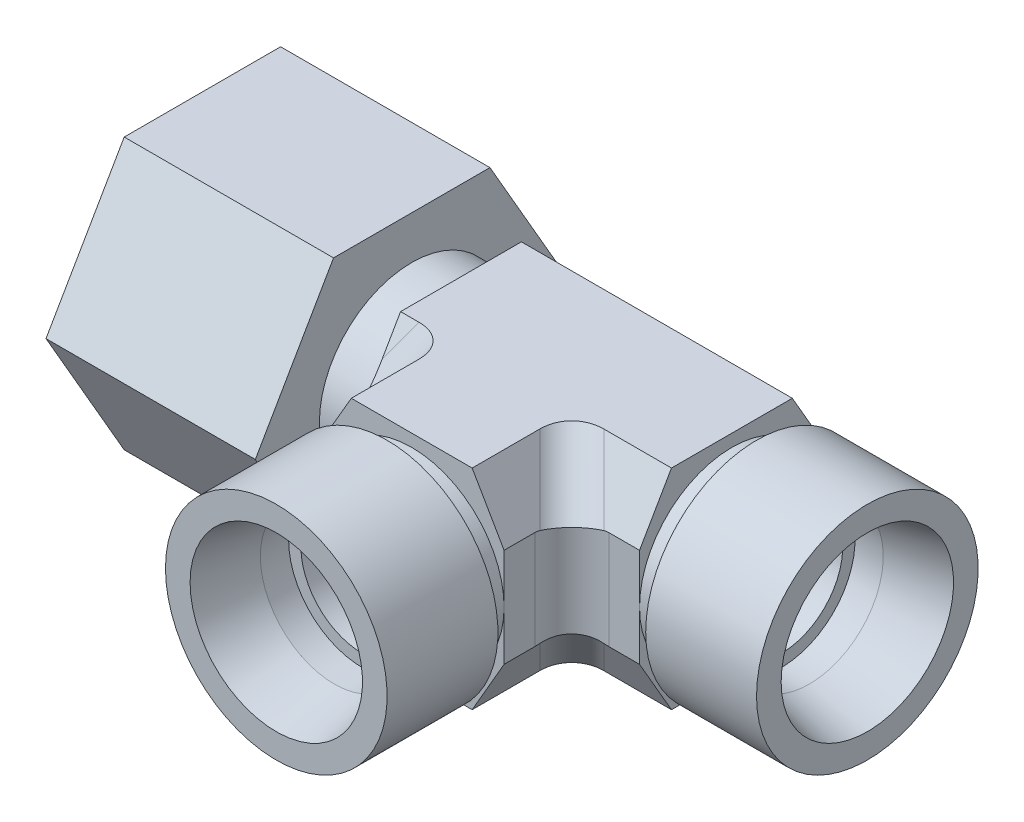
SolidWorks part; units mm, degrees
ref_plane "Plane1" through (0, 0, 0) normal (0, 0, 1) x (1, 0, 0)
ref_plane "Plane2" through (0, 0, 0) normal (0, 1, 0) x (1, 0, 0)
ref_plane "Plane3" through (0, 0, 0) normal (1, 0, 0) x (0, 0, -1)
sketch "Sketch1" plane through (0, 0, 0) normal (0, 1, 0) x (1, 0, 0)
  line L0 (-29.5, 0) -> (24, 0) construction
  line L1 (24, 0) -> (24, 9)
  line L2 (24, 9) -> (15, 9)
  line L3 (15, 9) -> (15, 7.5)
  line L4 (15, 7.5) -> (-13, 7.5)
  line L5 (-13, 7.5) -> (-13, 11)
  line L6 (-13, 11) -> (-30, 11)
  line L7 (-29.5, 6) -> (-29.5, 0)
  line L8 (-30, 11) -> (-30, 8.25)
  line L9 (-30, 8.25) -> (-23, 8.25)
  line L10 (-29.5, 0) -> (24, 0)
  line L12 (-23, 8.25) -> (-23, 6)
  line L13 (0, 0) -> (0, -32.9025) construction
  line L14 (-23, 6) -> (-29.5, 6)
  point P0 (-30, 0)
  dimension "Længde" = 54
  dimension "Indv. dia. omløber" = 16.5
  dimension "S3 længde" = 17
  dimension "Dybde på omløber" = 7
  dimension "L1" = 29.5
  dimension "M længde" = 9
revolve "Revolve1" add sketch "Sketch1" angle 360 about L10
sketch "Sketch2" plane through (0, 0, 0) normal (0, 1, 0) x (1, 0, 0)
  line L0 (0, 0) -> (0, -41.5691) construction
  line L1 (0, 0) -> (7.5, 0)
  line L2 (7.5, 0) -> (7.5, -15)
  line L3 (7.5, -15) -> (9, -15)
  line L4 (9, -15) -> (9, -24)
  line L5 (9, -24) -> (0, -24)
  line L6 (0, 0) -> (55.2214, 0) construction
  line L7 (0, 0) -> (0, -24)
  dimension "M længde" = 9
revolve "Revolve2" add sketch "Sketch2" angle 360 about L7
sketch "Sketch3" plane through (0, 0, 0) normal (1, 0, 0) x (0, 0, -1)
  line L0 (-7.5, 4.0096) -> (-7.5, -4.0096)
  line L1 (7.5, 4.0096) -> (4.9075, 8.5)
  line L2 (4.9075, 8.5) -> (-4.9075, 8.5)
  line L3 (-4.9075, 8.5) -> (-7.5, 4.0096)
  line L4 (-7.5, -4.0096) -> (-4.9075, -8.5)
  line L5 (-4.9075, -8.5) -> (4.9075, -8.5)
  line L6 (4.9075, -8.5) -> (7.5, -4.0096)
  line L7 (7.5, 4.0096) -> (7.5, -4.0096)
  circle A0 centre (0, 0) radius 8.5 construction
  circle A3 centre (0, 0) radius 7.5 construction
extrude "Extrude1" add sketch "Sketch3" along normal blind 9 and the other way blind 13
sketch "Sketch4" plane through (0, 0, 0) normal (0, 0, 1) x (1, 0, 0)
  line L0 (7.5, 4.0096) -> (7.5, -4.0096)
  line L1 (7.5, 4.0096) -> (4.9075, 8.5)
  line L2 (4.9075, 8.5) -> (-4.9075, 8.5)
  line L3 (-4.9075, 8.5) -> (-7.5, 4.0096)
  line L4 (-7.5, -4.0096) -> (-4.9075, -8.5)
  line L5 (-4.9075, -8.5) -> (4.9075, -8.5)
  line L6 (4.9075, -8.5) -> (7.5, -4.0096)
  line L7 (-7.5, 4.0096) -> (-7.5, -4.0096)
  circle A0 centre (0, 0) radius 8.5 construction
  circle A1 centre (0, 0) radius 7.5 construction
extrude "Extrude2" add sketch "Sketch4" along normal blind 13
sketch "Sketch5" plane through (0, 0, 0) normal (0, 1, 0) x (1, 0, 0)
  line L0 (-30, 0) -> (24, 0) construction
  line L1 (-30, 11) -> (-30, -11) construction
  line L2 (24, -9) -> (24, 9) construction
  line L3 (24, 0) -> (24, 7)
  line L4 (24, 7) -> (19.2954, 6)
  line L5 (19.2954, 6) -> (17, 6)
  line L6 (17, 6) -> (17, 5)
  line L7 (17, 5) -> (-5, 5)
  line L8 (-5, 5) -> (-5, 4)
  line L9 (-5, 4) -> (-30, 4)
  line L10 (-30, 4) -> (-30, 0)
  line L11 (0, 0) -> (0, -24) construction
  line L12 (-9, -24) -> (9, -24) construction
  line L13 (-30, 0) -> (24, 0)
  dimension "l" = 17
  dimension "samme som l8" = 7
  dimension "Indv. dia. (side m. omløber)" = 8
  dimension "vinkel" = 12
revolve "Cut-Revolve1" cut sketch "Sketch5" angle 360 about L13
sketch "Sketch6" plane through (0, 0, 0) normal (0, 1, 0) x (1, 0, 0)
  line L0 (0, 0) -> (0, -24) construction
  line L1 (-9, -24) -> (9, -24) construction
  line L2 (0, 0) -> (5, 0)
  line L3 (5, 0) -> (5, -17)
  line L4 (5, -17) -> (6, -17)
  line L5 (6, -17) -> (6, -19.2954)
  line L6 (6, -19.2954) -> (7, -24)
  line L7 (7, -24) -> (0, -24)
  line L8 (0, 0) -> (0, -24)
  dimension "l8" = 7
  dimension "vinkel" = 12
revolve "Cut-Revolve2" cut sketch "Sketch6" angle 360 about L0
sketch "Sketch7" plane through (-30, 0, 0) normal (-1, 0, 0) x (0, 0, 1)
  line L1 (-12.7017, 0) -> (-6.3509, -11)
  line L2 (-6.3509, -11) -> (6.3509, -11)
  line L3 (6.3509, -11) -> (12.7017, 0)
  line L4 (12.7017, 0) -> (6.3509, 11)
  line L5 (6.3509, 11) -> (-6.3509, 11)
  line L6 (-6.3509, 11) -> (-12.7017, 0)
  circle A0 centre (0, 0) radius 11 construction
  circle A1 centre (0, 0) radius 8.25 construction
  circle A2 centre (0, 0) radius 8.25
extrude "Extrude3" add sketch "Sketch7" against normal up to surface (17 mm away) up to face at (-13, 0, 11)
fillet "Fillet1" radius 3 6 edges at (6.2037, -6.2548, 6.2037) (6.2037, 6.2548, 6.2037) (-6.2037, -6.2548, 6.2037) (-6.2037, 6.2548, 6.2037) (7.5, 0, 7.5) (-7.5, 0, 7.5)
sketch "Sketch9" [suppressed] plane through (-43.8, 0, 0) normal (1, 0, 0) x (0, 0, -1)
  circle A0 centre (0, 0) radius 7 construction
  circle A1 centre (0, 0) radius 7
extrude "Cut-Extrude1" [suppressed] cut sketch "Sketch9" against normal through all
